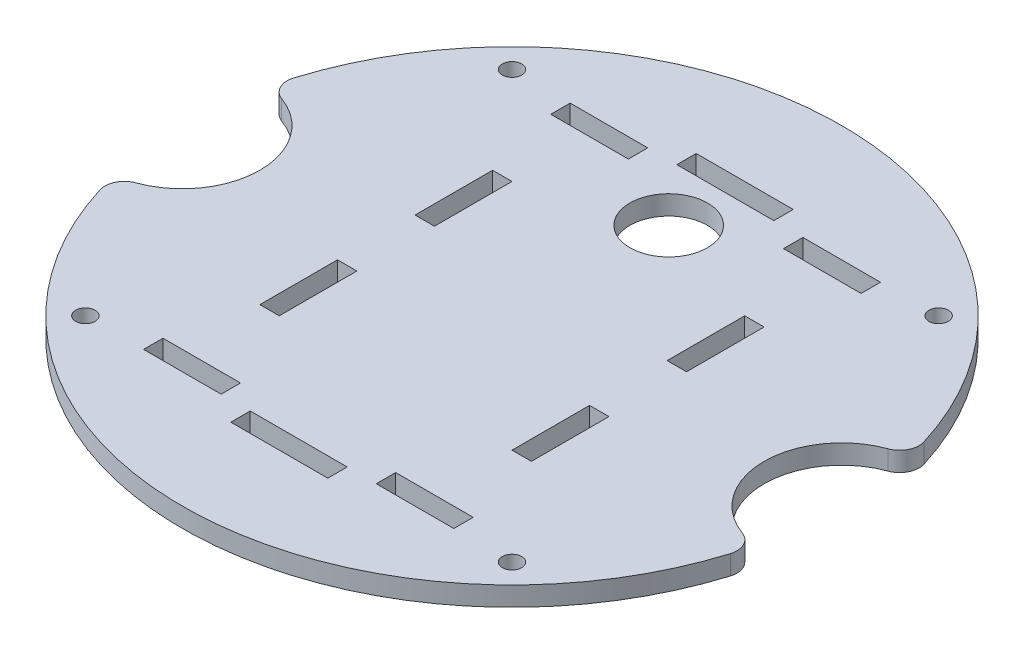
SolidWorks part; units mm, degrees
material "Pine"
ref_plane "Front Plane" through (0, 0, 0) normal (0, 0, 1) x (1, 0, 0)
ref_plane "Top Plane" through (0, 0, 0) normal (0, 1, 0) x (1, 0, 0)
ref_plane "Right Plane" through (0, 0, 0) normal (1, 0, 0) x (0, 0, -1)
sketch "Sketch1" plane through (0, 0, 0) normal (0, 1, 0) x (1, 0, 0)
  line L0 (0, 0) -> (0, 123.9148) construction
  line L1 (0, 0) -> (144.4711, 0) construction
  line L2 (-50.8, 63.5) -> (-25.4, 63.5)
  line L3 (-50.8, 63.5) -> (-50.8, 69.85)
  line L4 (-50.8, 69.85) -> (-25.4, 69.85)
  line L5 (-25.4, 63.5) -> (-25.4, 69.85)
  line L6 (25.4, 63.5) -> (25.4, 69.85)
  line L7 (50.8, 69.85) -> (25.4, 69.85)
  line L8 (50.8, 63.5) -> (50.8, 69.85)
  line L9 (50.8, 63.5) -> (25.4, 63.5)
  line L10 (-25.4, -63.5) -> (-25.4, -69.85)
  line L11 (-50.8, -63.5) -> (-25.4, -63.5)
  line L12 (-50.8, -63.5) -> (-50.8, -69.85)
  line L13 (-50.8, -69.85) -> (-25.4, -69.85)
  line L14 (50.8, -63.5) -> (50.8, -69.85)
  line L15 (50.8, -69.85) -> (25.4, -69.85)
  line L16 (25.4, -63.5) -> (25.4, -69.85)
  line L17 (50.8, -63.5) -> (25.4, -63.5)
  line L18 (38.1, -38.1) -> (44.45, -38.1)
  line L19 (38.1, 38.1) -> (44.45, 38.1)
  line L20 (38.1, 38.1) -> (38.1, 12.7)
  line L21 (38.1, 12.7) -> (44.45, 12.7)
  line L22 (44.45, 38.1) -> (44.45, 12.7)
  line L23 (38.1, -38.1) -> (38.1, -12.7)
  line L24 (38.1, -12.7) -> (44.45, -12.7)
  line L25 (44.45, -38.1) -> (44.45, -12.7)
  line L26 (-38.1, -38.1) -> (-44.45, -38.1)
  line L27 (-44.45, -38.1) -> (-44.45, -12.7)
  line L28 (-38.1, -38.1) -> (-38.1, -12.7)
  line L29 (-38.1, -12.7) -> (-44.45, -12.7)
  line L30 (-38.1, 12.7) -> (-44.45, 12.7)
  line L31 (-38.1, 38.1) -> (-38.1, 12.7)
  line L32 (-38.1, 38.1) -> (-44.45, 38.1)
  line L33 (-44.45, 38.1) -> (-44.45, 12.7)
  line L34 (-15.875, 69.85) -> (-15.875, 76.2)
  line L35 (15.875, -69.85) -> (-15.875, -69.85)
  line L36 (15.875, -69.85) -> (15.875, -76.2)
  line L37 (15.875, -76.2) -> (-15.875, -76.2)
  line L38 (-15.875, -69.85) -> (-15.875, -76.2)
  line L39 (15.875, -69.85) -> (-15.875, -76.2) construction
  line L40 (15.875, -76.2) -> (-15.875, -69.85) construction
  line L41 (15.875, 76.2) -> (-15.875, 76.2)
  line L42 (15.875, 69.85) -> (15.875, 76.2)
  line L43 (15.875, 69.85) -> (-15.875, 69.85)
  arc A0 (-103.1875, -31.7103) -> (103.1875, -31.7103) centre (0, 0) ccw
  circle A1 centre (0, 51.308) radius 12.7
  arc A2 (-99.2841, -23.876) -> (-99.2841, 23.876) centre (-107.95, 0) ccw
  arc A3 (-99.2841, 23.876) -> (-103.1875, 31.7103) centre (-97.1176, 29.845) cw
  arc A4 (-99.2841, -23.876) -> (-103.1875, -31.7103) centre (-97.1176, -29.845) ccw
  arc A5 (99.2841, -23.876) -> (103.1875, -31.7103) centre (97.1176, -29.845) cw
  arc A6 (99.2841, -23.876) -> (99.2841, 23.876) centre (107.95, 0) cw
  arc A7 (99.2841, 23.876) -> (103.1875, 31.7103) centre (97.1176, 29.845) ccw
  arc A8 (103.1875, 31.7103) -> (-103.1875, 31.7103) centre (0, 0) ccw
  arc A9 (-45.5479, 35.848) -> (-44.724, 34.5501) centre (-21.02, 50.5079) ccw construction
  arc A11 (4.8996, 51.4681) -> (6.3068, 52.0475) centre (4.7824, 53.7511) ccw construction
  point P52 (0, -73.025)
  point P61 (-45.1446, 35.1935)
  point P66 (5.6528, 51.6373)
  dimension "D1" = 215.9
  dimension "D10" = 25.4
  dimension "D12" = 50.8
  dimension "D13" = 6.35
  dimension "D14" = 6.35
  dimension "D11" = 51.308
  dimension "D2" = 25.4
  dimension "D3" = 25.4
  dimension "D4" = 6.35
  dimension "D5" = 63.5
  dimension "D6" = 6.35
  dimension "D7" = 25.4
  dimension "D8" = 12.7
  dimension "D9" = 38.1
  dimension "D15" = 31.75
  dimension "D16" = 6.35
extrude "Boss-Extrude1" add sketch "Sketch1" along normal blind 6.35
sketch "Sketch2" plane through (0, 0, 0) normal (0, -1, 0) x (1, 0, 0)
  line L0 (0, 0) -> (0, 99.3828) construction
  line L1 (0, 0) -> (-150.0844, 0) construction
  circle A0 centre (-69.85, 69.85) radius 3.175
  circle A1 centre (69.85, 69.85) radius 3.175
  circle A2 centre (69.85, -69.85) radius 3.175
  circle A3 centre (-69.85, -69.85) radius 3.175
  dimension "D1" = 6.35
extrude "Cut-Extrude1" cut sketch "Sketch2" against normal up to surface (6.35 mm away) up to face at (0, 6.35, 73.025)
